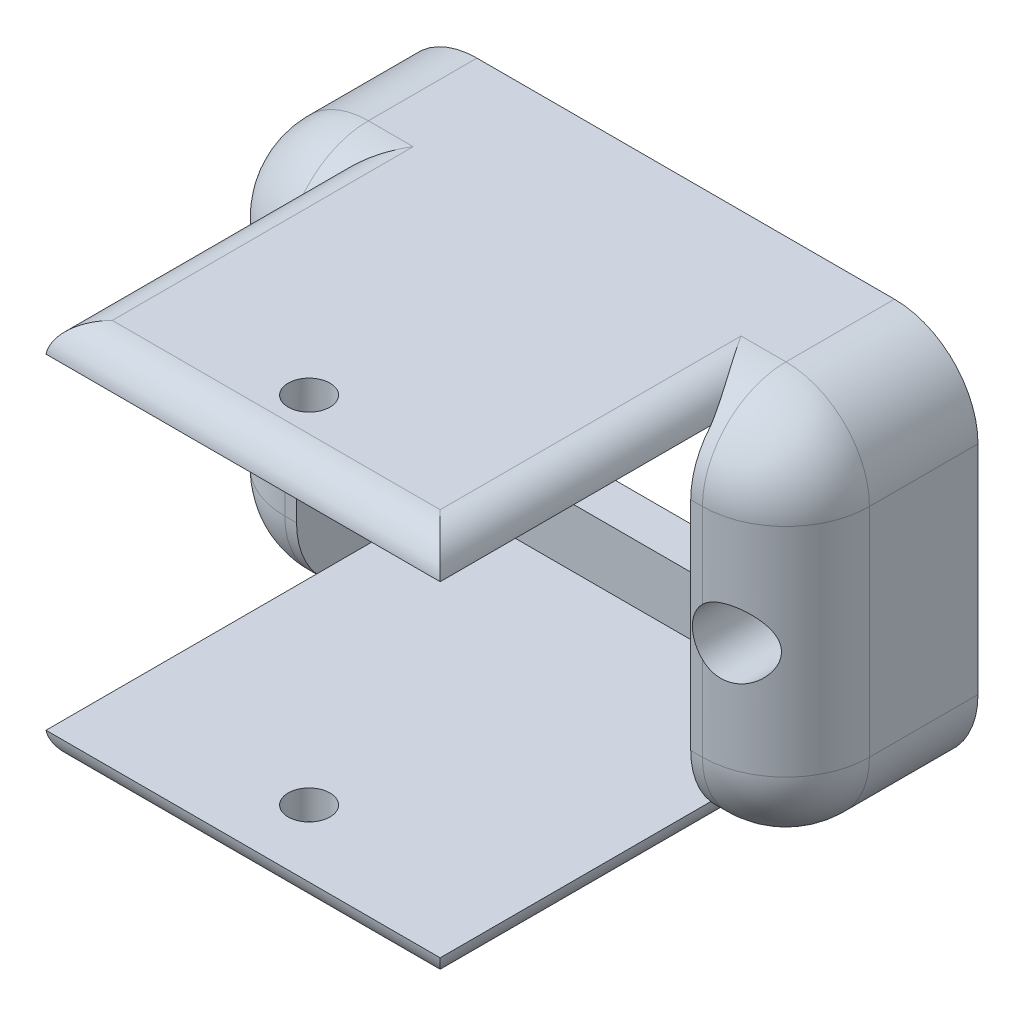
SolidWorks part; units mm, degrees
ref_plane "Front Plane" through (0, 0, 0) normal (0, 0, 1) x (1, 0, 0)
ref_plane "Top Plane" through (0, 0, 0) normal (0, 1, 0) x (1, 0, 0)
ref_plane "Right Plane" through (0, 0, 0) normal (1, 0, 0) x (0, 0, -1)
sketch "Sketch1" plane through (0, 0, 0) normal (0, 0, 1) x (1, 0, 0)
  line L1 (-17.5, -11.5) -> (17.5, -11.5)
  line L2 (-17.5, -11.5) -> (-17.5, 11.5)
  line L3 (-17.5, 11.5) -> (17.5, 11.5)
  line L4 (17.5, -11.5) -> (17.5, 11.5)
  line L5 (-17.5, -11.5) -> (17.5, 11.5) construction
  line L6 (-17.5, 11.5) -> (17.5, -11.5) construction
  line L7 (-11.8, -6.25) -> (11.8, -6.25)
  line L8 (-11.8, -6.25) -> (-11.8, 6.25)
  line L9 (-11.8, 6.25) -> (11.8, 6.25)
  line L10 (11.8, -6.25) -> (11.8, 6.25)
  line L11 (-11.8, -6.25) -> (11.8, 6.25) construction
  line L12 (-11.8, 6.25) -> (11.8, -6.25) construction
  point P0 (0, 0)
  point P6 (0, 0)
  dimension "D1" = 23
  dimension "D2" = 35
  dimension "D3" = 23.6
  dimension "D4" = 12.5
extrude "Boss-Extrude1" add sketch "Sketch1" along normal blind 2.5
sketch "Sketch6" plane through (0, 0, 2.5) normal (0, 0, 1) x (1, 0, 0)
  line L0 (-17.5, 11.5) -> (-17.5, -11.5)
  line L1 (-17.5, -11.5) -> (17.5, -11.5)
  line L2 (17.5, -11.5) -> (17.5, 11.5)
  line L3 (17.5, 11.5) -> (-17.5, 11.5)
  line L4 (-11.8, 6.25) -> (-11.8, 11.5) construction
  line L5 (11.8, 6.25) -> (11.8, 11.5) construction
  line L6 (11.8, 11.5) -> (11.8, -11.5) construction
  line L7 (-11.8, -6.25) -> (-11.8, -11.5) construction
  line L8 (-11.8, 9.75) -> (11.8, 9.75)
  line L9 (11.8, 9.75) -> (11.8, -9.75)
  line L10 (11.8, -9.75) -> (-11.8, -9.75)
  line L11 (-11.8, -9.75) -> (-11.8, 9.75)
  line L12 (11.8, 6.25) -> (-11.8, 6.25) construction
  line L13 (-11.8, -6.25) -> (11.8, -6.25) construction
  dimension "D1" = 3.5
  dimension "D2" = 3.5
extrude "Boss-Extrude2" add sketch "Sketch6" along normal blind 9
sketch "Sketch8" plane through (0, 0, 11.5) normal (0, 0, 1) x (1, 0, 0)
  line L0 (11.8, -9.75) -> (11.8, -11.5)
  line L1 (-17.5, -11.5) -> (17.5, -11.5) construction
  line L2 (-11.8, -9.75) -> (-11.8, -11.5)
  line L3 (-11.8, -9.75) -> (11.8, -9.75) construction
  line L4 (-11.8, -11.5) -> (11.8, -11.5)
  line L5 (-11.8, -9.75) -> (11.8, -9.75)
  line L6 (11.8, 9.75) -> (11.8, 11.5)
  line L7 (17.5, 11.5) -> (-17.5, 11.5) construction
  line L8 (11.8, 9.75) -> (-11.8, 9.75)
  line L9 (-11.8, 9.75) -> (-11.8, 11.5)
  line L10 (-11.8, 11.5) -> (11.8, 11.5)
extrude "Boss-Extrude3" add sketch "Sketch8" along normal blind 15
sketch "Sketch9" plane through (0, 11.5, 0) normal (0, 1, 0) x (1, 0, 0)
  line L0 (11.8, -26.5) -> (-11.8, -26.5) construction
  line L1 (11.8, -26.5) -> (11.8, -11.5) construction
  circle A0 centre (-0.05, -22.5) radius 1.25
  dimension "D2" = 2.5
  dimension "D3" = 4
  dimension "D1" = 11.85
extrude "Cut-Extrude1" cut sketch "Sketch9" against normal through all
sketch "Sketch11" plane through (0, 0, 11.5) normal (0, 0, 1) x (1, 0, 0)
  line L2 (-17.5, 0) -> (17.5, 0) construction
  line L3 (-17.5, 11.5) -> (-17.5, -11.5) construction
  line L4 (17.5, -11.5) -> (17.5, 11.5) construction
  line L5 (-11.8, 9.75) -> (-11.8, -9.75) construction
  line L6 (0, 0) -> (0, 6.25) construction
  line L7 (11.8, 6.25) -> (-11.8, 6.25) construction
  circle A0 centre (-13.9, 0) radius 2
  circle A1 centre (13.9, 0) radius 2
  dimension "D1" = 4
  dimension "D2" = 2.1
extrude "Cut-Extrude2" cut sketch "Sketch11" against normal blind 8
sketch "Sketch13" plane through (0, 0, 3.5) normal (0, 0, 1) x (1, 0, 0)
  line L0 (0, 0) -> (0, 5.0709) construction
  circle A0 centre (-13.9, 0) radius 1.15
  circle A1 centre (13.9, 0) radius 1.15
  dimension "D1" = 2.3
extrude "Cut-Extrude3" cut sketch "Sketch13" against normal through all
fillet "Fillet1" radius 2 6 edges at (-11.8, 11.5, 19) (0, 11.5, 26.5) (11.8, 11.5, 19) (11.8, -11.5, 19) (0, -11.5, 26.5) (-11.8, -11.5, 19)
fillet "Fillet2" radius 5 4 edges at (17.5, -11.5, 5.75) (-17.5, -11.5, 5.75) (-17.5, 11.5, 5.75) (17.5, 11.5, 5.75)
fillet "Fillet3" radius 5 10 edges at (11.1578, -11.5, 11.5) (11.1578, 11.5, 11.5) (16.0355, 10.0355, 11.5) (17.5, 0, 11.5) (-11.1578, 11.5, 11.5) (-16.0355, 10.0355, 11.5) (-17.5, 0, 11.5) (-11.1578, -11.5, 11.5) (16.0355, -10.0355, 11.5) (-16.0355, -10.0355, 11.5)
